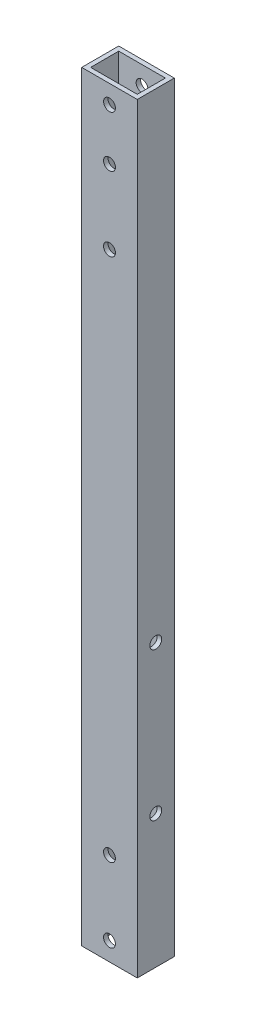
SolidWorks part; units mm, degrees
ref_plane "正面" through (0, 0, 0) normal (0, 0, 1) x (1, 0, 0)
ref_plane "平面" through (0, 0, 0) normal (0, 1, 0) x (1, 0, 0)
ref_plane "右側面" through (0, 0, 0) normal (1, 0, 0) x (0, 0, -1)
sketch "ｽｹｯﾁ1" plane through (0, 0, 0) normal (0, 1, 0) x (1, 0, 0)
  line L0 (-6.3, 3.8) -> (6.3, 3.8)
  line L1 (-7.5, 5) -> (7.5, 5)
  line L2 (-7.5, 5) -> (-7.5, -5)
  line L3 (-7.5, -5) -> (7.5, -5)
  line L4 (7.5, 5) -> (7.5, -5)
  line L5 (-7.5, 5) -> (7.5, -5) construction
  line L6 (-7.5, -5) -> (7.5, 5) construction
  line L7 (6.3, 3.8) -> (6.3, -3.8)
  line L8 (-6.3, -3.8) -> (6.3, -3.8)
  line L9 (-6.3, 3.8) -> (-6.3, -3.8)
  point P0 (0, 0)
  dimension "D1" = 15
  dimension "D2" = 10
  dimension "D3" = 1.2
extrude "ﾎﾞｽ - 押し出し1" add sketch "ｽｹｯﾁ1" along normal mid plane 220
sketch "ｽｹｯﾁ2" plane through (0, 0, -5) normal (0, 0, -1) x (-1, 0, 0)
  line L0 (0, -110) -> (0, -85) construction
  line L1 (-7.5, -110) -> (7.5, -110) construction
  circle A0 centre (0, -85) radius 1.6
  circle A1 centre (0, -105) radius 1.6
  dimension "D2" = 3.2
  dimension "D3" = 3.2
  dimension "D1" = 25
  dimension "D4" = 20
extrude "ｶｯﾄ - 押し出し1" cut sketch "ｽｹｯﾁ2" against normal blind 100
sketch "ｽｹｯﾁ3" plane through (7.5, 0, 0) normal (1, 0, 0) x (0, 0, -1)
  line L1 (0, -110) -> (0, 0) construction
  line L2 (-5, -110) -> (5, -110) construction
  line L4 (6.5084, -36.5) -> (31.5068, -36.5)
  line L5 (31.5068, -36.5) -> (31.5068, -31.5)
  line L6 (31.5068, -31.5) -> (6.5084, -31.5)
  line L7 (6.5084, -31.5) -> (6.5084, -36.5)
  line L8 (6.5084, -36.5) -> (31.5068, -36.5) construction
  line L10 (31.5068, -31.5) -> (6.5084, -31.5) construction
  line L11 (6.5084, -31.5) -> (6.5084, -36.5) construction
  line L12 (6.5084, -76.5) -> (31.5068, -76.5)
  line L13 (31.5068, -76.5) -> (31.5068, -71.5)
  line L14 (31.5068, -71.5) -> (6.5084, -71.5)
  line L15 (6.5084, -71.5) -> (6.5084, -76.5)
  line L16 (6.5084, -76.5) -> (31.5068, -76.5) construction
  line L18 (31.5068, -71.5) -> (6.5084, -71.5) construction
  line L19 (6.5084, -71.5) -> (6.5084, -76.5) construction
  line L26 (31.5068, -36.5) -> (31.5068, -31.5)
  line L27 (31.5068, -76.5) -> (31.5068, -71.5)
  circle A0 centre (0, -34) radius 1.6
  circle A1 centre (0, -74) radius 1.6
  dimension "D3" = 3.2
  dimension "D4" = 3.2
  dimension "D5" = 36
  dimension "D6" = 40
  dimension "D1" = 0
  dimension "D2" = 0
extrude "ｶｯﾄ - 押し出し2" cut sketch "ｽｹｯﾁ3" against normal blind 15 contours A0 | A1 region at (7.5, -34, 0) region at (7.5, -74, 0)
sketch "ｽｹｯﾁ5" plane through (0, 110, 0) normal (0, 1, 0) x (1, 0, 0)
  line L4 (7.5, -5) -> (7.5, 5)
  line L5 (7.5, 5) -> (-7.5, 5)
  line L6 (-7.5, 5) -> (-7.5, -5)
  line L7 (-7.5, -5) -> (7.5, -5)
  line L8 (7.5, -5) -> (7.5, 5)
  line L9 (7.5, 5) -> (-7.5, 5)
  line L10 (-7.5, 5) -> (-7.5, -5)
  line L11 (-7.5, -5) -> (7.5, -5)
  dimension "D1" = 0
extrude "ｶｯﾄ - 押し出し4" cut sketch "ｽｹｯﾁ5" against normal blind 14.5
sketch "ｽｹｯﾁ6" plane through (0, 0, -5) normal (0, 0, -1) x (-1, 0, 0)
  line L0 (0, 95.5) -> (0, 90.5) construction
  line L1 (-7.5, 95.5) -> (7.5, 95.5) construction
  line L2 (0, 90.5) -> (0, 76.66) construction
  line L3 (0, 76.66) -> (0, 56.66) construction
  circle A0 centre (0, 90.5) radius 1.6
  circle A1 centre (0, 76.66) radius 1.6
  circle A2 centre (0, 56.66) radius 1.6
  dimension "D2" = 3.2
  dimension "D5" = 3.2
  dimension "D6" = 3.2
  dimension "D1" = 5
  dimension "D3" = 13.84
  dimension "D4" = 20
extrude "ｶｯﾄ - 押し出し5" cut sketch "ｽｹｯﾁ6" against normal blind 15
